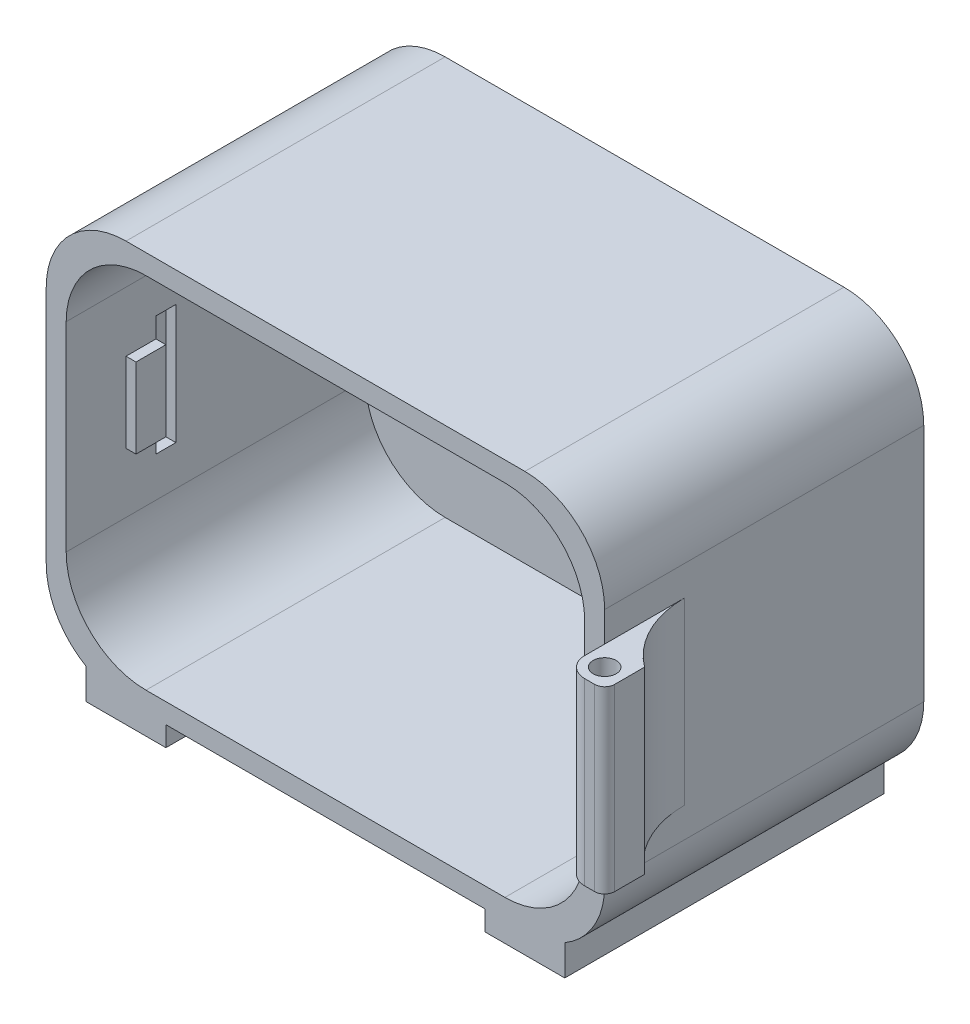
SolidWorks part; units mm, degrees
ref_plane "Front Plane" through (0, 0, 0) normal (0, 0, 1) x (1, 0, 0)
ref_plane "Top Plane" through (0, 0, 0) normal (0, 1, 0) x (1, 0, 0)
ref_plane "Right Plane" through (0, 0, 0) normal (1, 0, 0) x (0, 0, -1)
sketch "Sketch1" plane through (0, 0, 0) normal (0, 0, 1) x (1, 0, 0)
  line L0 (-82.55, 31.75) -> (-82.55, -31.75)
  line L1 (-63.5, 63.5) -> (63.5, 63.5)
  line L2 (-88.9, 38.1) -> (-88.9, -38.1)
  line L3 (-63.5, -63.5) -> (63.5, -63.5)
  line L4 (88.9, 38.1) -> (88.9, -38.1)
  line L5 (-88.9, 63.5) -> (88.9, -63.5) construction
  line L6 (-88.9, -63.5) -> (88.9, 63.5) construction
  line L7 (-57.15, -57.15) -> (57.15, -57.15)
  line L8 (82.55, 31.75) -> (82.55, -31.75)
  line L9 (-57.15, 57.15) -> (57.15, 57.15)
  line L10 (-88.9, 63.5) -> (88.9, 63.5) construction
  line L11 (88.9, 63.5) -> (88.9, -63.5) construction
  line L12 (82.55, 57.15) -> (82.55, -57.15) construction
  line L13 (-82.55, 57.15) -> (82.55, 57.15) construction
  line L14 (-82.55, -57.15) -> (82.55, -57.15) construction
  line L15 (-88.9, -63.5) -> (88.9, -63.5) construction
  line L16 (-82.55, 57.15) -> (-82.55, -57.15) construction
  line L17 (-88.9, 63.5) -> (-88.9, -63.5) construction
  arc A0 (63.5, 63.5) -> (88.9, 38.1) centre (63.5, 38.1) cw
  arc A1 (82.55, 31.75) -> (57.15, 57.15) centre (57.15, 31.75) ccw
  arc A2 (57.15, -57.15) -> (82.55, -31.75) centre (57.15, -31.75) ccw
  arc A3 (63.5, -63.5) -> (88.9, -38.1) centre (63.5, -38.1) ccw
  arc A4 (-82.55, -31.75) -> (-57.15, -57.15) centre (-57.15, -31.75) ccw
  arc A5 (-88.9, -38.1) -> (-63.5, -63.5) centre (-63.5, -38.1) ccw
  arc A6 (-63.5, 63.5) -> (-88.9, 38.1) centre (-63.5, 38.1) ccw
  arc A7 (-82.55, 31.75) -> (-57.15, 57.15) centre (-57.15, 31.75) cw
  point P0 (0, 0)
  dimension "D4" = 25.4
  dimension "D1" = 177.8
  dimension "D2" = 127
  dimension "D3" = 6.35
extrude "Boss-Extrude1" add sketch "Sketch1" against normal blind 95.25
sketch "Sketch2" plane through (0, 0, -95.25) normal (0, 0, -1) x (-1, 0, 0)
  line L0 (-63.5, 63.5) -> (63.5, 63.5)
  line L1 (-63.5, 63.5) -> (63.5, 63.5) construction
  line L2 (0, 63.5) -> (0, -63.5) construction
  line L3 (63.5, -63.5) -> (-63.5, -63.5) construction
  line L4 (63.5, -63.5) -> (-63.5, -63.5)
  line L5 (-88.9, -38.1) -> (-88.9, 38.1) construction
  line L6 (-88.9, -38.1) -> (-88.9, 38.1)
  line L7 (88.9, -38.1) -> (88.9, 38.1)
  arc A0 (-88.9, 38.1) -> (-63.5, 63.5) centre (-63.5, 38.1) cw
  arc A1 (-63.5, -63.5) -> (-88.9, -38.1) centre (-63.5, -38.1) cw
  arc A2 (-88.9, -38.1) -> (-63.5, -63.5) centre (-63.5, -38.1) ccw construction
  arc A3 (63.5, -63.5) -> (88.9, -38.1) centre (63.5, -38.1) ccw
  arc A4 (88.9, 38.1) -> (63.5, 63.5) centre (63.5, 38.1) ccw
extrude "Boss-Extrude2" add sketch "Sketch2" along normal blind 6.35
sketch "Sketch4" plane through (0, -63.5, 0) normal (0, -1, 0) x (1, 0, 0)
  line L0 (-76.2, 0) -> (-50.8, 0)
  line L2 (-76.2, 0) -> (-76.2, -101.6)
  line L3 (-88.9, -101.6) -> (-63.5, -101.6) construction
  line L4 (-76.2, -101.6) -> (-50.8, -101.6)
  line L5 (63.5, -101.6) -> (-63.5, -101.6) construction
  line L6 (-50.8, -101.6) -> (-50.8, 0)
  line L7 (0, 0) -> (0, -101.6) construction
  line L8 (-63.5, 0) -> (63.5, 0) construction
  line L9 (76.2, -101.6) -> (50.8, -101.6)
  line L10 (76.2, 0) -> (76.2, -101.6)
  line L11 (76.2, 0) -> (50.8, 0)
  line L12 (50.8, -101.6) -> (50.8, 0)
  point P4 (-63.5, 0)
  dimension "D1" = 25.4
extrude "Boss-Extrude3" add sketch "Sketch4" along normal blind 6.35 and the other way up to next
sketch "Sketch5" plane through (0, 0, 0) normal (0, 1, 0) x (1, 0, 0)
  line L0 (0, 0) -> (88.9, 0) construction
  line L1 (63.5, 0) -> (-63.5, 0) construction
  line L2 (95.25, 0) -> (101.6, 0) construction
  line L3 (88.9, 25.4) -> (88.9, 0)
  line L4 (95.25, 0) -> (95.25, -6.35) construction
  line L7 (101.6, -12.7) -> (88.9, -12.7)
  line L8 (101.6, -12.7) -> (101.6, 0)
  line L9 (101.6, 0) -> (95.25, 0)
  line L10 (88.9, -12.7) -> (88.9, 0)
  line L11 (101.6, -12.7) -> (88.9, 0) construction
  line L12 (101.6, 0) -> (88.9, -12.7) construction
  line L13 (88.9, -6.35) -> (101.6, -6.35) construction
  arc A3 (101.6, 0) -> (88.9, 25.4) centre (120.65, 25.4) cw
  circle A4 centre (95.25, -6.35) radius 3.675
  point P4 (98.425, 0)
  dimension "D2" = 7.35
  dimension "D1" = 6.35
  dimension "D3" = 88.9
  dimension "D4" = 25.4
extrude "Boss-Extrude5" add sketch "Sketch5" along normal blind 28.575 and the other way blind 28.575 contours A3 L3 L10 L7 L8 A4 region at (94.0273, 0, 0.7656)
fillet "Fillet1" radius 3.175 1 edges at (101.6, 0, 12.7)
sketch "Sketch6" plane through (0, 28.575, 0) normal (0, 1, 0) x (1, 0, 0)
  line L0 (91.575, -6.35) -> (88.9, -6.35) construction
  line L1 (88.9, 0) -> (88.9, -12.7) construction
  line L2 (97.1007, -9.525) -> (101.6, -9.525) construction
  circle A0 centre (95.25, -6.35) radius 3.675 construction
sketch "Sketch8" plane through (-82.55, 0, 0) normal (1, 0, 0) x (0, 0, -1)
  line L0 (0, -19.05) -> (28.575, -19.05) construction
  line L1 (0, 31.75) -> (0, -31.75) construction
  line L2 (28.575, -19.05) -> (34.925, -19.05)
  line L3 (34.925, -19.05) -> (34.925, 19.05)
  line L4 (34.925, 19.05) -> (28.575, 19.05)
  line L5 (28.575, 19.05) -> (28.575, -19.05)
  line L6 (95.25, -57.15) -> (0, -57.15) construction
  dimension "D1" = 28.575
  dimension "D2" = 6.35
  dimension "D3" = 38.1
  dimension "D4" = 38.1
extrude "Cut-Extrude1" cut sketch "Sketch8" against normal blind 3.175
sketch "Sketch10" plane through (-82.55, 0, 0) normal (1, 0, 0) x (0, 0, -1)
  line L0 (28.575, 0) -> (28.575, 12.7) construction
  line L1 (28.575, 19.05) -> (28.575, -19.05) construction
  line L3 (28.575, 12.7) -> (19.05, 12.7)
  line L4 (28.575, 12.7) -> (28.575, -12.7)
  line L5 (28.575, -12.7) -> (19.05, -12.7)
  line L6 (19.05, 12.7) -> (19.05, -12.7)
  point P7 (28.575, 0)
  dimension "D1" = 12.7
  dimension "D2" = 9.525
extrude "Boss-Extrude6" add sketch "Sketch10" along normal blind 3.175
sketch "Sketch11" plane through (0, 0, -101.6) normal (0, 0, -1) x (-1, 0, 0)
  line L0 (32.462, -188.0741) -> (352.462, -188.0741) construction
  line L1 (-8.558, 38.2776) -> (9.4147, 38.2776)
  line L2 (9.4147, 38.2776) -> (12.3761, 30.5166)
  line L3 (12.3761, 30.5166) -> (6.5554, 30.5166)
  line L4 (-8.558, 38.2776) -> (-26.541, -14.1457)
  line L5 (-26.541, -14.1457) -> (-20.9531, -14.1457)
  line L6 (-20.9531, -17.5278) -> (-27.8644, -17.5278)
  line L7 (-27.8644, -17.5278) -> (-30.0702, -24.7333)
  line L8 (-30.0702, -24.7333) -> (-9.6303, -24.7333)
  line L9 (-9.6303, -24.7333) -> (-7.4245, -17.5278)
  line L10 (-7.4245, -17.5278) -> (8.4569, -17.5278)
  line L11 (8.4569, -17.5278) -> (10.5156, -24.7333)
  line L12 (10.5156, -24.7333) -> (12.3761, -24.7333)
  line L13 (12.3761, -24.7333) -> (12.3761, -18.8513)
  line L14 (16.1034, -18.8513) -> (16.1034, -24.7333)
  line L15 (16.1034, -24.7333) -> (21.2502, -24.7333)
  line L16 (21.2502, -24.7333) -> (21.2502, -18.8513)
  line L17 (24.3382, -18.8513) -> (24.3382, -24.7333)
  line L18 (24.3382, -24.7333) -> (31.2496, -24.7333)
  line L19 (31.2496, -24.7333) -> (13.3095, 27.1753)
  line L20 (13.3095, 27.1753) -> (6.5554, 27.1753)
  line L21 (0.7548, 15.0295) -> (-4.8523, -6.6891)
  line L22 (-4.8523, -6.6891) -> (6.0184, -6.6891)
  line L23 (6.0184, -6.6891) -> (0.7548, 15.0295)
  arc A0 (6.5554, 30.5166) -> (6.5554, 27.1753) centre (2.9252, 28.8459) ccw
  arc A1 (12.3761, -18.8513) -> (16.1034, -18.8513) centre (14.2398, -15.2135) cw
  arc A2 (-20.9531, -14.1457) -> (-20.9531, -17.5278) centre (-17.0513, -15.8368) cw
  arc A3 (21.2502, -18.8513) -> (24.3382, -18.8513) centre (22.7942, -15.1977) cw
  circle A4 centre (2.9252, 28.8459) radius 1.6706
  circle A5 centre (-17.0513, -15.8368) radius 2.045
  circle A6 centre (14.2398, -15.2135) radius 2.3144
  circle A7 centre (22.7942, -15.1977) radius 1.5563
  circle A8 centre (0, 3.175) radius 44.8241
  dimension "D1" = 3.175
extrude "Cut-Extrude4" cut sketch "Sketch11" against normal blind 1.5875 contours A8 | L22 L23 L21 | A3 L17 L18 L19 L20 A0 L3 L2 L1 L4 L5 A2 L6 L7 L8 L9 L10 L11 L12 L13 A1 L14 L15 L16
fillet "Fillet2" radius 6.35 1 edges at (88.9, 0, 12.7)
